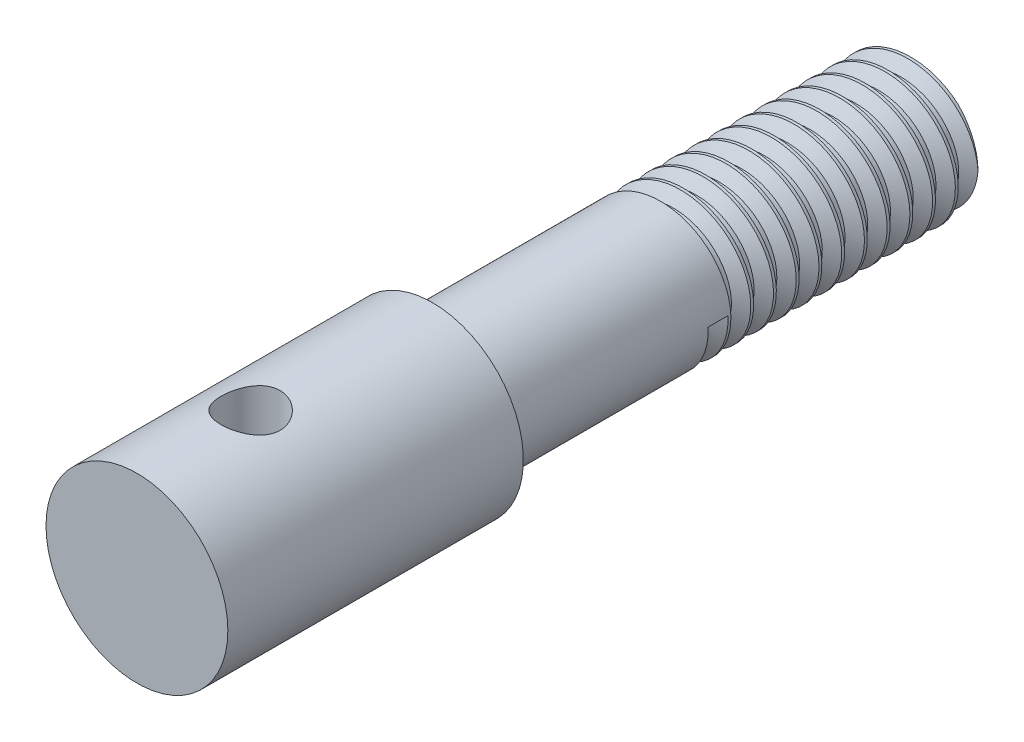
SolidWorks part; units mm, degrees
ref_plane "Alzado" through (0, 0, 0) normal (0, 0, 1) x (1, 0, 0)
ref_plane "Planta" through (0, 0, 0) normal (0, 1, 0) x (1, 0, 0)
ref_plane "Vista lateral" through (0, 0, 0) normal (1, 0, 0) x (0, 0, -1)
sketch "Croquis1" plane through (0, 0, 0) normal (0, 0, 1) x (1, 0, 0)
  circle A0 centre (0, 0) radius 4
  dimension "D1" = 8
extrude "Saliente-Extruir1" add sketch "Croquis1" along normal blind 38
ref_plane "Plano1" through (0, 4, 0) normal (0, 1, 0) x (1, 0, 0)
sketch "Croquis2" plane through (0, 4, 0) normal (0, 1, 0) x (1, 0, 0)
  line L0 (-4, -38) -> (4, -38) construction
  line L1 (-4, 0) -> (-4, -38) construction
  circle A0 centre (0, -33) radius 1.3
  dimension "D1" = 2.6
  dimension "D2" = 5
  dimension "D3" = 4
extrude "Cortar-Extruir1" cut sketch "Croquis2" against normal through all
sketch "Croquis3" plane through (0, 0, 0) normal (0, 0, -1) x (-1, 0, 0)
  circle A0 centre (0, 0) radius 3
  circle A2 centre (0, 0) radius 4
  dimension "D1" = 6
  dimension "D2" = 8
extrude "Cortar-Extruir2" cut sketch "Croquis3" against normal blind 25
thread "Rosca1" pitch 1 method cut profile "Perfil de rosca1" start angle 0, offset 0, length 15, pitch 1, diameter 6
ref_plane "Plano2" through (3, 0, 0) normal (0, -1, 0) x (1, 0, 0)
sketch "Perfil de rosca1" plane through (3, 0, 0) normal (0, -1, 0) x (1, 0, 0)
  line L0 (0, 0) -> (0, 1) construction
  line L11 (0, 0) -> (0, 0.875)
  line L12 (0, 0.875) -> (-0.5413, 0.5625)
  line L13 (-0.5413, 0.5625) -> (-0.5413, 0.3125)
  line L15 (-0.5413, 0.3125) -> (0, 0)
  line L17 (-0.5413, 0.4375) -> (0, 0.4375) construction
  point P2 (0, 0)
  dimension "Pitch" = 1
  dimension "Profile_Angle" = 60
  dimension "Profile_Land" = 0.25
  dimension "Profile_Height" = 0.5413
ref_plane "Plano3" through (0, 4, 0) normal (0, 1, 0) x (1, 0, 0)
sketch "Croquis8" plane through (0, 4, 0) normal (0, 1, 0) x (1, 0, 0)
  line L0 (-10, 0) -> (10, 0)
  line L1 (-10, 0) -> (-10, -4)
  line L2 (-10, -4) -> (10, -4)
  line L3 (10, -4) -> (10, 0)
  line L4 (3, 0) -> (-3, 0) construction
  line L5 (0, 0) -> (0, 3.2967) construction
  dimension "D1" = 4
  dimension "D2" = 20
extrude "Cortar-Extruir3" cut sketch "Croquis8" against normal through all
